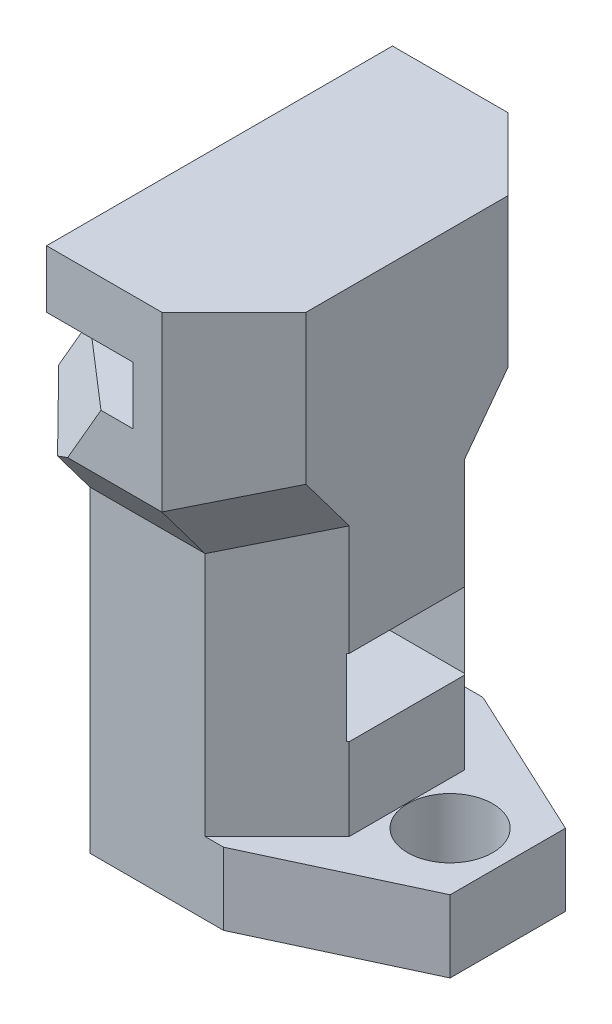
SolidWorks part; units mm, degrees
ref_plane "Front Plane" through (0, 0, 0) normal (0, 0, 1) x (1, 0, 0)
ref_plane "Top Plane" through (0, 0, 0) normal (0, 1, 0) x (1, 0, 0)
ref_plane "Right Plane" through (0, 0, 0) normal (1, 0, 0) x (0, 0, -1)
sketch "Sketch1" plane through (0, 0, 0) normal (0, 0, 1) x (1, 0, 0)
  line L0 (-9, 8) -> (4, 8)
  line L1 (4, 8) -> (4, -30)
  line L2 (4, -30) -> (-14, -30)
  line L3 (-14, -30) -> (-14, 0)
  line L5 (-14, 0) -> (-3, 0)
  line L6 (-3, 0) -> (-3, 4)
  line L8 (-3, 4) -> (-9, 4)
  line L9 (-9, 4) -> (-9, 8)
  line L10 (0, -13.2) -> (0, 13.2) construction
  line L11 (13.2, 0) -> (-13.2, 0) construction
  dimension "D1" = 6
  dimension "D2" = 13
  dimension "D3" = 4
  dimension "D4" = 18
  dimension "D5" = 30
  dimension "D6" = 4
  dimension "D7" = 4
extrude "Boss-Extrude1" add sketch "Sketch1" along normal mid plane 24
sketch "Sketch2" plane through (0, -30, 0) normal (0, -1, 0) x (1, 0, 0)
  line L0 (13.75, 0) -> (-13.75, 0) construction
  line L1 (-14, 12) -> (-14, -12) construction
  circle A0 centre (-5, 0) radius 5.25
  dimension "D1" = 10.5
  dimension "D2" = 9
extrude "Cut-Extrude1" cut sketch "Sketch2" against normal blind 6
chamfer "Chamfer2" distance 3 angle 60 1 edges at (-14, 0, 0) first distance on face at (-8.5, 0, 0)
sketch "Sketch4" plane through (0, -30, 0) normal (0, -1, 0) x (1, 0, 0)
  circle A0 centre (-5, 0) radius 2.75
  dimension "D1" = 5.5
extrude "Cut-Extrude3" cut sketch "Sketch4" against normal blind 28
sketch "Sketch5" plane through (4, 0, 0) normal (1, 0, 0) x (0, 0, -1)
  line L0 (0, 13.75) -> (0, -13.75) construction
  line L1 (-4.1, -14) -> (4.1, -14)
  line L2 (-4.1, -14) -> (-4.1, -19.3)
  line L3 (-4.1, -19.3) -> (4.1, -19.3)
  line L4 (4.1, -14) -> (4.1, -19.3)
  line L5 (13.2, 0) -> (-13.2, 0) construction
  dimension "D1" = 8.2
  dimension "D2" = 4.1
  dimension "D3" = 5.3
  dimension "D4" = 14
extrude "Cut-Extrude4" cut sketch "Sketch5" against normal up to next
sketch "Sketch7" plane through (4, 0, 0) normal (1, 0, 0) x (0, 0, -1)
  line L0 (-12, -30) -> (-12, -4)
  line L1 (-12, -30) -> (-12, 8) construction
  line L2 (-12, -4) -> (-9, -8)
  line L3 (-9, -8) -> (-9, -30)
  line L4 (-12, -30) -> (12, -30) construction
  line L5 (-9, -30) -> (-12, -30)
  line L6 (0, 9.1764) -> (0, -31.2342) construction
  line L7 (0, 13.75) -> (0, -13.75) construction
  line L8 (9, -30) -> (12, -30)
  line L9 (9, -8) -> (9, -30)
  line L10 (12, -4) -> (9, -8)
  line L11 (12, -30) -> (12, -4)
  dimension "D1" = 26
  dimension "D2" = 22
  dimension "D3" = 3
extrude "Cut-Extrude6" cut sketch "Sketch7" against normal up to next
chamfer "Chamfer3" distance 5 angle 45 12 edges at (4, -19, 9) (4, -6, 10.5) (4, 2, 12) (4, 2, -12) (4, -6, -10.5) (4, -19, -9) (-14, -19, -9) (-14, -6.5981, -10.0514) (-12.1547, -2, -12) (-12.1547, -2, 12) (-14, -6.5981, 10.0514) (-14, -19, 9)
sketch "Sketch8" plane through (0, -30, 0) normal (0, -1, 0) x (1, 0, 0)
  line L0 (4, 4) -> (-1, 9)
  line L1 (-1, 9) -> (11, 9)
  line L2 (11, 9) -> (11, -9)
  line L3 (4, 4) -> (4, -4) construction
  line L4 (4, -4) -> (4, 4)
  line L5 (11, -9) -> (-1, -9)
  line L6 (-1, -9) -> (4, -4)
  circle A0 centre (7, 0) radius 2.95
  dimension "D2" = 5.9
  dimension "D1" = 12
  dimension "D3" = 3
  dimension "D4" = 4
extrude "Boss-Extrude2" add sketch "Sketch8" against normal blind 5
chamfer "Chamfer4" distance 5 angle 65 2 edges at (11, -27.5, -9) (11, -27.5, 9) first distance on face at (11, -27.5, 0)
